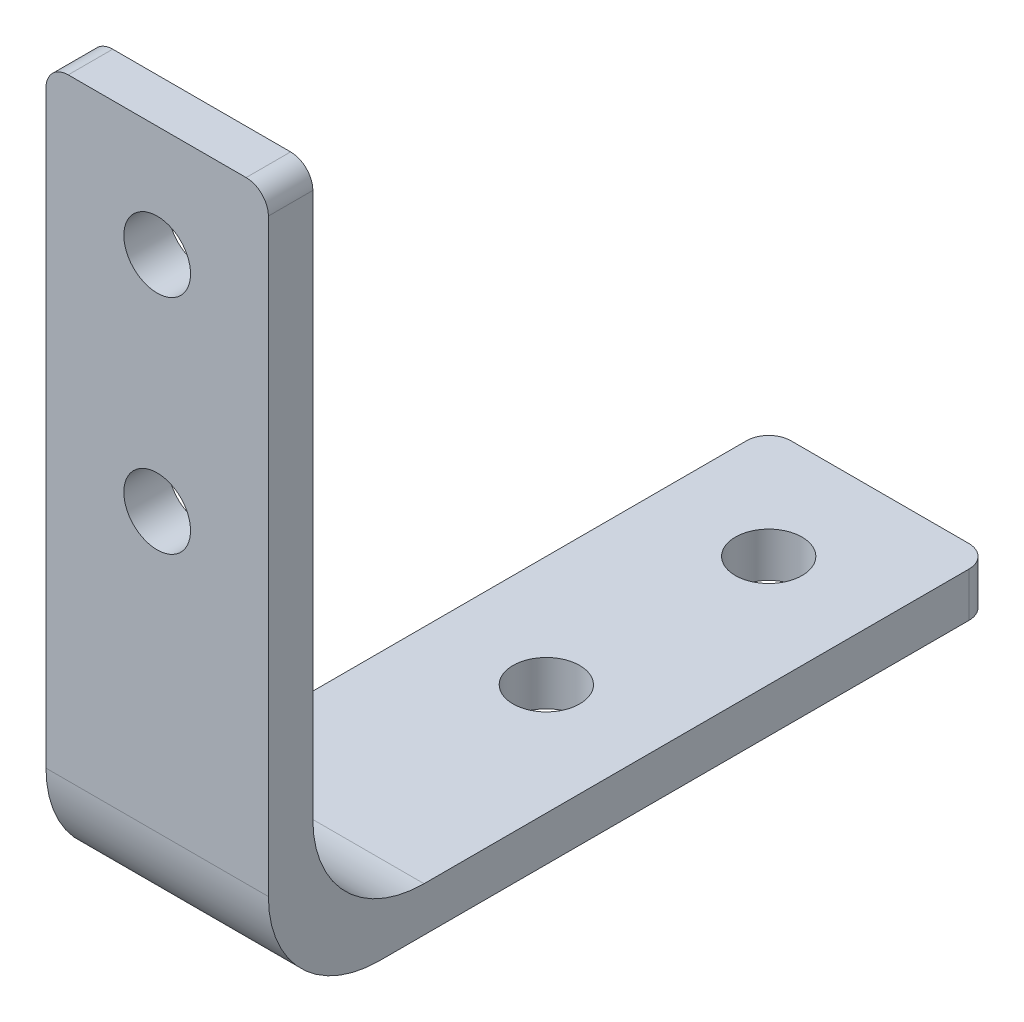
SolidWorks part; units mm, degrees
material "1060 Alloy"
ref_plane "Спереди" through (0, 0, 0) normal (0, 0, 1) x (1, 0, 0)
ref_plane "Сверху" through (0, 0, 0) normal (0, 1, 0) x (1, 0, 0)
ref_plane "Справа" through (0, 0, 0) normal (1, 0, 0) x (0, 0, -1)
sketch "Эскиз1" plane through (0, 0, 0) normal (1, 0, 0) x (0, 0, -1)
  line L0 (0, 32.5) -> (0, 0)
  line L1 (0, 0) -> (32.5, 0)
  line L2 (32.5, 0) -> (32.5, 2)
  line L3 (32.5, 2) -> (2, 2)
  line L4 (2, 2) -> (2, 32.5)
  line L5 (2, 32.5) -> (0, 32.5)
  dimension "D1" = 32.5
  dimension "D2" = 32.5
  dimension "D3" = 2
extrude "Бобышка-Вытянуть1" add sketch "Эскиз1" along normal blind 5 and the other way blind 5
sketch "Эскиз2" plane through (0, 2, 0) normal (0, 1, 0) x (1, 0, 0)
  line L0 (-5, 32.5) -> (5, 32.5) construction
  line L1 (-10.7235, 22.5) -> (49989.2765, 22.5) construction
  circle A0 centre (0, 27.5) radius 1.5
  circle A1 centre (0, 17.5) radius 1.5
  dimension "D1" = 3
  dimension "D2" = 5
  dimension "D3" = 5
extrude "Вырез-Вытянуть1" cut sketch "Эскиз2" against normal through all
sketch "Эскиз3" plane through (0, 0, -2) normal (0, 0, -1) x (-1, 0, 0)
  line L0 (5, 32.5) -> (-5, 32.5) construction
  line L1 (13.3016, 22.5) -> (-49986.6984, 22.5) construction
  circle A0 centre (0, 27.5) radius 1.5
  circle A1 centre (0, 17.5) radius 1.5
  dimension "D1" = 3
  dimension "D2" = 5
  dimension "D3" = 5
extrude "Вырез-Вытянуть2" cut sketch "Эскиз3" against normal through all
fillet "Скругление1" radius 1 4 edges at (-5, 1, -32.5) (5, 1, -32.5) (5, 32.5, -1) (-5, 32.5, -1)
fillet "Скругление2" radius 5 2 edges at (0, 0, 0) (0, 2, -2)
